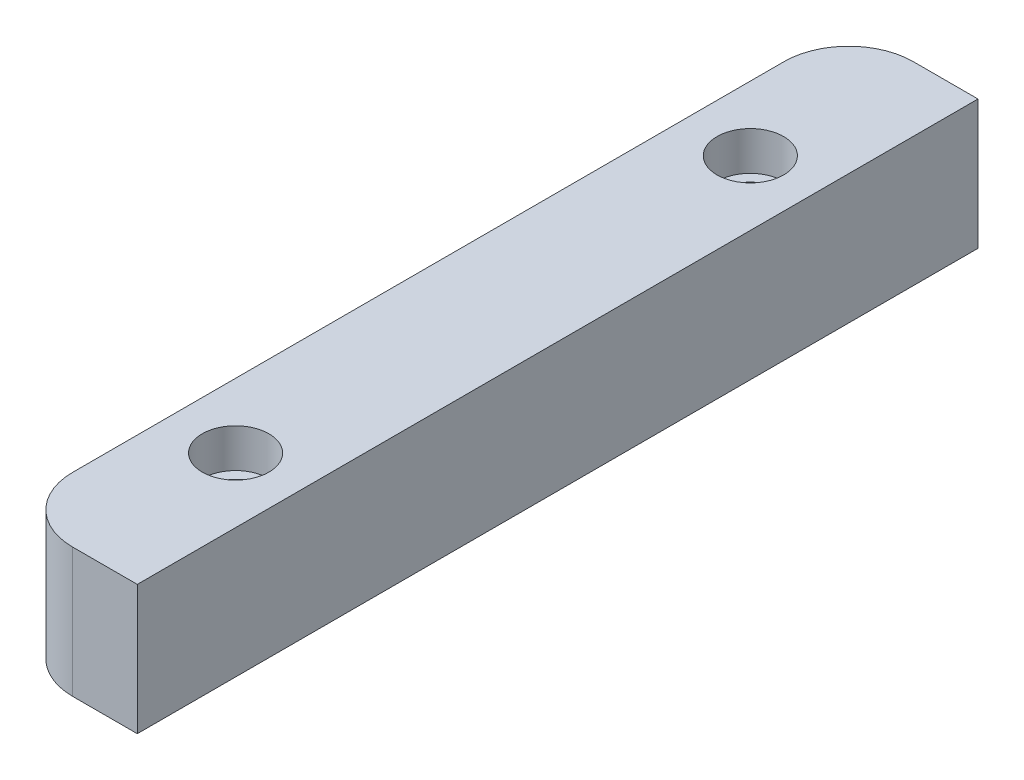
SolidWorks part; units mm, degrees
ref_plane "Ebene vorne" through (0, 0, 0) normal (0, 0, 1) x (1, 0, 0)
ref_plane "Ebene oben" through (0, 0, 0) normal (0, 1, 0) x (1, 0, 0)
ref_plane "Ebene rechts" through (0, 0, 0) normal (1, 0, 0) x (0, 0, -1)
sketch "Skizze2" plane through (0, 0, 0) normal (0, 1, 0) x (1, 0, 0)
  line L0 (-32.5, 32.5) -> (-32.5, -32.5) construction
  line L1 (42.5, 32.5) -> (-42.5, 32.5)
  line L2 (42.5, 32.5) -> (42.5, -32.5)
  line L3 (42.5, -32.5) -> (-42.5, -32.5)
  line L4 (-42.5, 32.5) -> (-42.5, -32.5)
  line L5 (42.5, 32.5) -> (-42.5, -32.5) construction
  line L6 (42.5, -32.5) -> (-42.5, 32.5) construction
  point P0 (0, 0)
  dimension "D1" = 65
  dimension "D2" = 85
  dimension "D3" = 10
extrude "Aufsatz-Linear austragen1" add sketch "Skizze2" along normal blind 5
sketch "Skizze3" plane through (0, 5, 0) normal (0, 1, 0) x (1, 0, 0)
  line L0 (-42.5, -32.5) -> (42.5, -32.5) construction
  line L1 (-42.5, 32.5) -> (-32.5, 32.5)
  line L2 (-42.5, 32.5) -> (-42.5, -32.5)
  line L3 (-42.5, -32.5) -> (-32.5, -32.5)
  line L4 (-32.5, 32.5) -> (-32.5, -32.5)
  dimension "D1" = 10
extrude "Aufsatz-Linear austragen2" add sketch "Skizze3" along normal blind 10
sketch "Skizze4" plane through (0, 0, 0) normal (0, 0, 1) x (1, 0, 0)
  line L0 (17.769, 0) -> (-25.9637, -28.6417)
  line L1 (-42.5, 0) -> (42.5, 0) construction
  line L2 (-25.9637, -28.6417) -> (-42.5, 0)
  line L9 (-42.5, 0) -> (42.5, 0)
  line L10 (42.5, 0) -> (42.5, 5)
  line L11 (42.5, 5) -> (-32.5, 5)
  line L12 (-32.5, 5) -> (-32.5, 15)
  line L13 (-32.5, 15) -> (-42.5, 15)
  line L14 (-42.5, 15) -> (-42.5, 0)
  line L15 (17.769, 0) -> (42.5, 0)
  line L16 (42.5, 0) -> (42.5, 5)
  line L17 (42.5, 5) -> (-32.5, 5)
  line L18 (-32.5, 5) -> (-32.5, 15)
  line L19 (-32.5, 15) -> (-42.5, 15)
  line L20 (-42.5, 15) -> (-42.5, 0)
  dimension "D1" = 60
  dimension "D2" = 0
extrude "Aufsatz-Linear austragen3" add sketch "Skizze4" along normal blind 15 and the other way blind 15
hole_wizard "Durchgangsloch für M61" positions "Skizze5" profile "Skizze6" hole size "M6" standard "DIN" end condition through all
sketch "Skizze5" plane through (-31.875, -18.403, 0) normal (-0.866, -0.5, 0) x (0, 0, 1)
  point P0 (0, 10.9797)
sketch "Skizze6" plane through (-37.3648, -8.8944, 0) normal (0, 0, 1) x (0.5, -0.866, 0)
  line L0 (0, 0) -> (0, 81.1122)
  line L1 (0, 81.1122) -> (3.3, 81.1122)
  line L2 (3.3, 81.1122) -> (3.3, 0)
  line L5 (3.3, 0) -> (0, 0)
  line L11 (0, -6.35) -> (0, 107.95) construction
  dimension "Bohrerdurchmesser" = 6.6
  dimension "Bohrungstiefe" = 81.1122
ref_plane "Ebene1" through (2.766, 1.597, 0) normal (-0.866, -0.5, 0) x (0, 0, 1)
sketch "Skizze7" plane through (2.766, 1.597, 0) normal (-0.866, -0.5, 0) x (0, 0, 1)
  circle A0 centre (0, 10.9797) radius 6.1263
extrude "Schnitt-Linear austragen1" cut sketch "Skizze7" along normal blind 30
sketch "Skizze8" plane through (-31.875, -18.403, 0) normal (-0.866, -0.5, 0) x (0, 0, 1)
  line L1 (-3, -7.953) -> (3, -7.953)
  line L2 (-3, -7.953) -> (-3, 2.047)
  line L3 (-3, 2.047) -> (3, 2.047)
  line L4 (3, -7.953) -> (3, 2.047)
  line L5 (-3, -7.953) -> (3, 2.047) construction
  line L6 (-3, 2.047) -> (3, -7.953) construction
  point P0 (0, -2.953)
  dimension "D1" = 10
  dimension "D2" = 6
extrude "Aufsatz-Linear austragen4" add sketch "Skizze8" along normal blind 3
fillet "Verrundung1" radius 2 2 edges at (-32.8985, -16.6303, 0) (-27.8985, -25.2906, 0)
fillet "Verrundung2" radius 10 2 edges at (-12.3655, 0, -15) (-12.3655, 0, 15)
fillet "Verrundung3" radius 5 4 edges at (-42.5, 7.5, -32.5) (-42.5, 7.5, 32.5) (42.5, 2.5, -32.5) (42.5, 2.5, 32.5)
fillet "Verrundung4" radius 5 4 edges at (13.2969, -2.9289, 17.9289) (13.2969, -2.9289, -17.9289) (-11.7318, -19.3209, 15) (-11.7318, -19.3209, -15)
sketch "Skizze9" plane through (0, 5, 0) normal (0, 1, 0) x (1, 0, 0)
  line L0 (1, -45.3373) -> (1, 49954.6627) construction
  line L1 (-32.5, -32.5) -> (-32.5, 32.5) construction
  line L2 (20.1281, 0) -> (-49979.8719, 0) construction
  line L3 (42.5, -27.5) -> (42.5, 27.5) construction
  line L4 (-37.5, 9.2268) -> (-37.5, 50009.2268) construction
  line L5 (-42.5, 27.5) -> (-42.5, -27.5) construction
  circle A0 centre (-23, 18) radius 1.75
  circle A1 centre (25, 18) radius 1.75
  circle A2 centre (-23, -18) radius 1.75
  circle A3 centre (25, -18) radius 1.75
  circle A4 centre (-37.5, 19.9) radius 1.75
  circle A5 centre (-37.5, -19.9) radius 1.75
  point P8 (42.5, 0)
  dimension "D2" = 3.5
  dimension "D6" = 3.5
  dimension "D1" = 33.5
  dimension "D3" = 48
  dimension "D4" = 36
  dimension "D5" = 5
  dimension "D7" = 39.8
extrude "Schnitt-Linear austragen2" cut sketch "Skizze9" against normal through all and the other way through all
sketch "Skizze11" plane through (0, 15, 0) normal (0, 1, 0) x (1, 0, 0)
  circle A0 centre (-37.5, -19.9) radius 1.75 construction
  circle A1 centre (-37.5, 19.9) radius 1.75 construction
  circle A2 centre (-37.5, -19.9) radius 1.75
  circle A3 centre (-37.5, 19.9) radius 1.75
  circle A4 centre (-37.5, 19.9) radius 2.575
  circle A5 centre (-37.5, -19.9) radius 2.575
  dimension "D1" = 5.15
  dimension "D2" = 5.15
extrude "Schnitt-Linear austragen4" cut sketch "Skizze11" against normal blind 3
sketch "Skizze10" plane through (0, 0, 0) normal (0, -1, 0) x (1, 0, 0)
  circle A0 centre (25, 18) radius 1.75 construction
  circle A1 centre (25, -18) radius 1.75 construction
  circle A2 centre (-23, -18) radius 1.75 construction
  circle A3 centre (-23, 18) radius 1.75 construction
  circle A4 centre (25, 18) radius 1.75 construction
  circle A5 centre (25, -18) radius 1.75 construction
  circle A6 centre (-23, -18) radius 1.75 construction
  circle A7 centre (-23, 18) radius 1.75 construction
  circle A8 centre (25, 18) radius 3
  circle A9 centre (25, -18) radius 3
  circle A10 centre (-23, -18) radius 3
  circle A11 centre (-23, 18) radius 3
  circle A12 centre (-37.5, -19.9) radius 1.75 construction
  circle A13 centre (-37.5, 19.9) radius 1.75 construction
  circle A14 centre (-37.5, -19.9) radius 1.75 construction
  circle A15 centre (-37.5, 19.9) radius 1.75 construction
  circle A16 centre (-37.5, 19.9) radius 3
  circle A17 centre (-37.5, -19.9) radius 3
  dimension "D1" = 6
  dimension "D2" = 6
  dimension "D3" = 6
  dimension "D4" = 6
  dimension "D5" = 6
  dimension "D6" = 6
extrude "Schnitt-Linear austragen3" cut sketch "Skizze10" against normal blind 1 and the other way through all
sketch "Skizze14" plane through (0, 5, 0) normal (0, 1, 0) x (1, 0, 0)
  line L1 (-48.4813, -36.7291) -> (48.4813, -36.7291)
  line L2 (-48.4813, -36.7291) -> (-48.4813, 36.7291)
  line L3 (-48.4813, 36.7291) -> (48.4813, 36.7291)
  line L4 (48.4813, -36.7291) -> (48.4813, 36.7291)
  line L5 (-48.4813, -36.7291) -> (48.4813, 36.7291) construction
  line L6 (-48.4813, 36.7291) -> (48.4813, -36.7291) construction
  point P0 (0, 0)
extrude "Schnitt-Linear austragen7" cut sketch "Skizze14" against normal through all
sketch "Skizze15" plane through (0, 5, 0) normal (0, -1, 0) x (1, 0, 0)
  line L0 (-37.5, -19.9) -> (-37.5, 49980.1) construction
  line L1 (-37.5, 0) -> (-20.0031, 0) construction
  line L3 (-38.75, -7.25) -> (-36.25, -7.25)
  line L4 (-38.75, -7.25) -> (-38.75, 7.25)
  line L5 (-38.75, 7.25) -> (-36.25, 7.25)
  line L6 (-36.25, -7.25) -> (-36.25, 7.25)
  line L7 (-38.75, -7.25) -> (-36.25, 7.25) construction
  line L8 (-38.75, 7.25) -> (-36.25, -7.25) construction
  point P5 (-37.5, 0)
  dimension "D1" = 14.5
  dimension "D2" = 2.5
extrude "Aufsatz-Linear austragen5" add sketch "Skizze15" along normal blind 2.8
